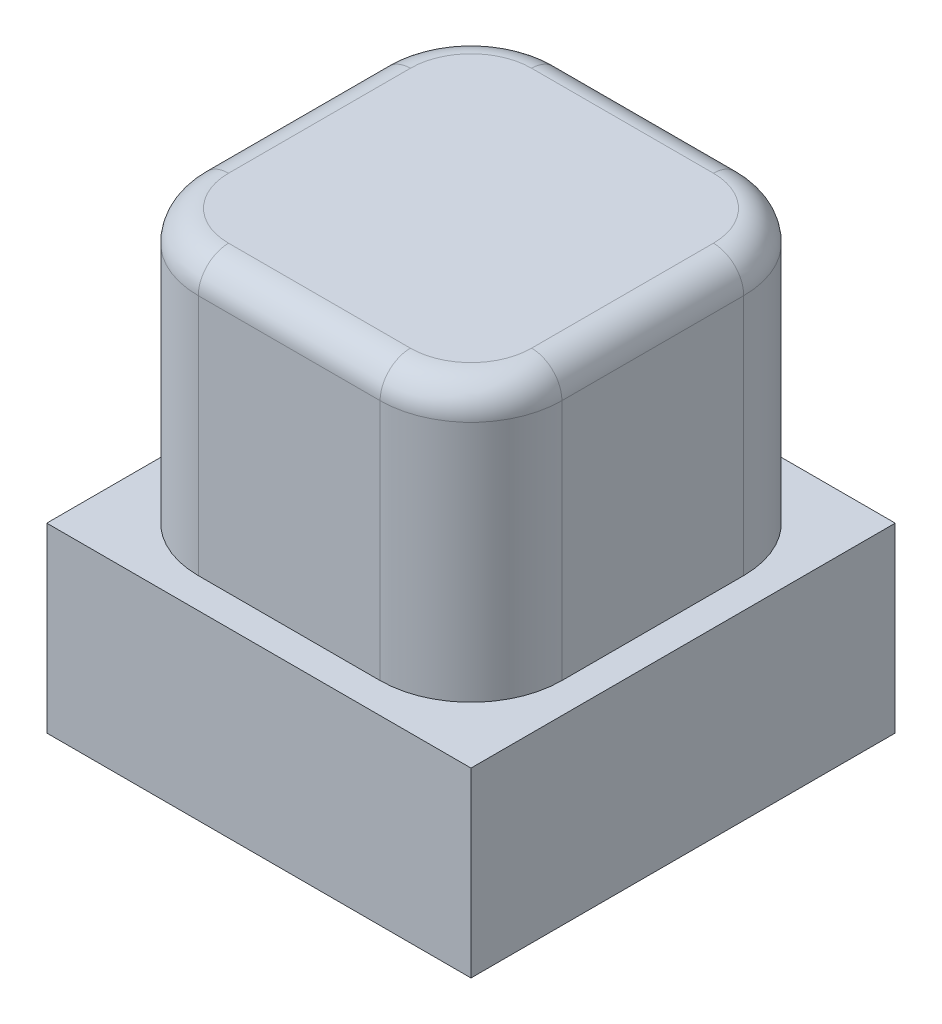
SolidWorks part; units mm, degrees
ref_plane "前视基准面" through (0, 0, 0) normal (0, 0, 1) x (1, 0, 0)
ref_plane "上视基准面" through (0, 0, 0) normal (0, 1, 0) x (1, 0, 0)
ref_plane "右视基准面" through (0, 0, 0) normal (1, 0, 0) x (0, 0, -1)
other "Configuration Table"
sketch "草图1" plane through (0, 0, 0) normal (0, 1, 0) x (1, 0, 0)
  line L1 (-3, -3) -> (3, -3)
  line L2 (-3, -3) -> (-3, 3)
  line L3 (-3, 3) -> (3, 3)
  line L4 (3, -3) -> (3, 3)
  line L5 (0, 3) -> (0, -3) construction
  line L6 (-3, 0) -> (3, 0) construction
  point P0 (0, 0)
  dimension "D1" = 6
extrude "凸台-拉伸1" add sketch "草图1" along normal blind 4.5
fillet "圆角1" radius 1.5 4 edges at (-3, 2.25, -3) (3, 2.25, -3) (3, 2.25, 3) (-3, 2.25, 3)
fillet "圆角3" radius 0.5 8 edges at (-2.5607, 4.5, 2.5607) (-2.5607, 4.5, -2.5607) (2.5607, 4.5, -2.5607) (2.5607, 4.5, 2.5607) (0, 4.5, -3) (3, 4.5, 0) (-3, 4.5, 0) (0, 4.5, 3)
sketch "草图2" plane through (0, 0, 0) normal (0, -1, 0) x (1, 0, 0)
  line L1 (-3.5, -3.5) -> (3.5, -3.5)
  line L2 (-3.5, -3.5) -> (-3.5, 3.5)
  line L3 (-3.5, 3.5) -> (3.5, 3.5)
  line L4 (3.5, -3.5) -> (3.5, 3.5)
  line L5 (0, 3.5) -> (0, -3.5) construction
  line L6 (-3.5, 0) -> (3.5, 0) construction
  point P0 (0, 0)
  dimension "D1" = 7
extrude "凸台-拉伸2" add sketch "草图2" along normal blind 4.7
ref_plane "基准面1" through (0, 0.3, 0) normal (0, 1, 0) x (1, 0, 0)
sketch "草图3" plane through (0, -4.7, 0) normal (0, -1, 0) x (1, 0, 0)
  circle A0 centre (0, 0) radius 2
  dimension "D1" = 4
sketch "草图4" plane through (0, 0.3, 0) normal (0, 1, 0) x (1, 0, 0)
  circle A0 centre (0, 0) radius 1.9
  dimension "D1" = 3.8
loft "切除-放样1" cut profiles "草图3", "草图4" connector at (1.9997, -4.7, -0.0339) connector at (1.8738, 0.3, 0.3147)
sketch "草图5" plane through (0, -4.7, 0) normal (0, -1, 0) x (1, 0, 0)
  line L1 (-3.5, 3.5) -> (3.5, 3.5)
  line L2 (-3.5, 3.5) -> (-3.5, -3.5)
  line L3 (-3.5, -3.5) -> (3.5, -3.5)
  line L4 (3.5, 3.5) -> (3.5, -3.5)
extrude "切除-拉伸1" cut sketch "草图5" against normal blind 1.7
